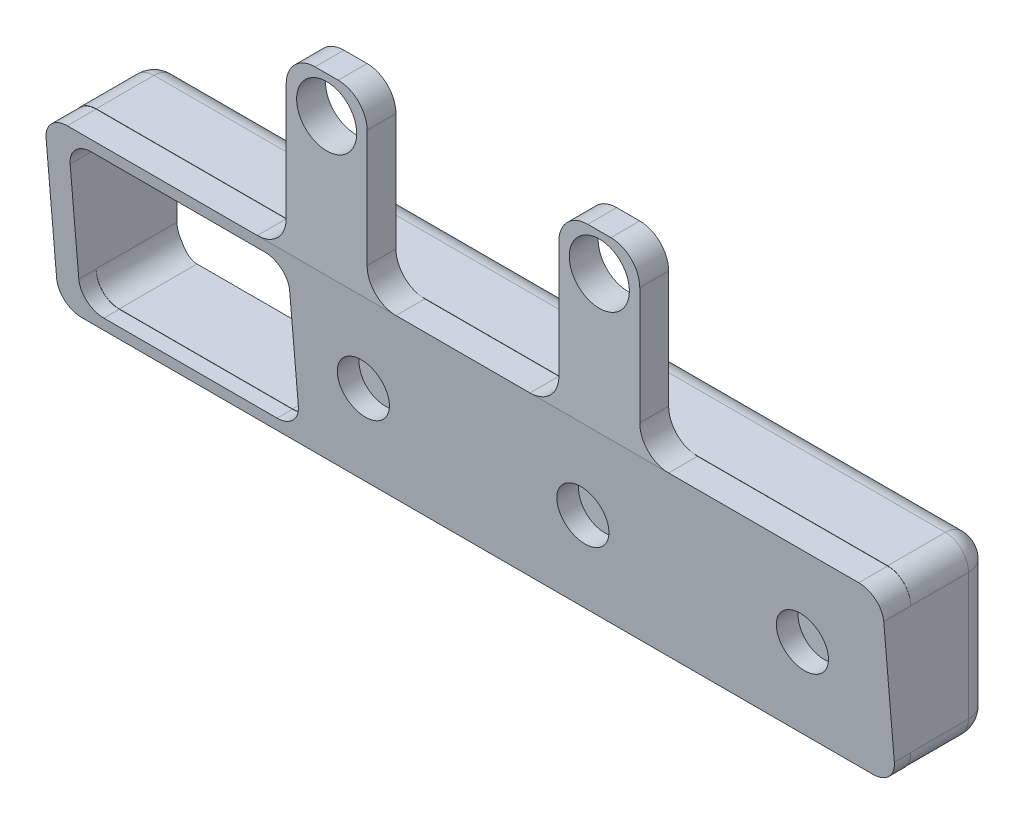
SolidWorks part; units mm, degrees
ref_plane "Front Plane" through (0, 0, 0) normal (0, 0, 1) x (1, 0, 0)
ref_plane "Top Plane" through (0, 0, 0) normal (0, 1, 0) x (1, 0, 0)
ref_plane "Right Plane" through (0, 0, 0) normal (1, 0, 0) x (0, 0, -1)
sketch "Sketch1" plane through (0, 0, 0) normal (0, 0, 1) x (1, 0, 0)
  line L0 (10.0074, 11.5687) -> (10.0074, -3.4313) construction
  line L1 (-24.2426, 11.5687) -> (-7.7926, 11.5687)
  line L2 (-26.2426, 9.5687) -> (-26.2426, -1.4313)
  line L3 (-24.2426, -3.4313) -> (44.2574, -3.4313)
  line L4 (46.2574, 9.5687) -> (46.2574, -1.4313)
  line L5 (-5.2926, 14.0687) -> (-5.2926, 24.2087)
  line L6 (-22.2426, 10.5687) -> (-7.2426, 10.5687)
  line L7 (-24.2426, 8.5687) -> (-24.2426, -0.4313)
  line L8 (-22.2426, -2.4313) -> (-7.2426, -2.4313)
  line L9 (-5.2426, 8.5687) -> (-5.2426, -0.4313)
  line L10 (-2.7926, 26.7087) -> (-0.7926, 26.7087)
  line L11 (1.7074, 24.2087) -> (1.7074, 14.0687)
  line L12 (18.3074, 14.0687) -> (18.3074, 24.2087)
  line L13 (20.8074, 26.7087) -> (22.8074, 26.7087)
  line L14 (25.3074, 24.2087) -> (25.3074, 14.0687)
  line L15 (4.2074, 11.5687) -> (15.8074, 11.5687)
  line L16 (27.8074, 11.5687) -> (44.2574, 11.5687)
  circle A0 centre (38.7574, 4.0687) radius 2.25
  circle A1 centre (19.7574, 4.0687) radius 2.25
  circle A2 centre (0.7574, 4.0687) radius 2.25
  arc A3 (-24.2426, -0.4313) -> (-22.2426, -2.4313) centre (-22.2426, -0.4313) ccw
  arc A4 (-7.2426, -2.4313) -> (-5.2426, -0.4313) centre (-7.2426, -0.4313) ccw
  arc A5 (-7.2426, 10.5687) -> (-5.2426, 8.5687) centre (-7.2426, 8.5687) cw
  arc A6 (-22.2426, 10.5687) -> (-24.2426, 8.5687) centre (-22.2426, 8.5687) ccw
  arc A7 (44.2574, -3.4313) -> (46.2574, -1.4313) centre (44.2574, -1.4313) ccw
  arc A8 (44.2574, 11.5687) -> (46.2574, 9.5687) centre (44.2574, 9.5687) cw
  arc A9 (-26.2426, -1.4313) -> (-24.2426, -3.4313) centre (-24.2426, -1.4313) ccw
  arc A10 (-24.2426, 11.5687) -> (-26.2426, 9.5687) centre (-24.2426, 9.5687) ccw
  circle A11 centre (-1.7926, 23.5087) radius 2.6
  arc A12 (-0.7926, 26.7087) -> (1.7074, 24.2087) centre (-0.7926, 24.2087) cw
  arc A13 (-5.2926, 24.2087) -> (-2.7926, 26.7087) centre (-2.7926, 24.2087) cw
  circle A14 centre (21.8074, 23.5087) radius 2.6
  arc A15 (22.8074, 26.7087) -> (25.3074, 24.2087) centre (22.8074, 24.2087) cw
  arc A16 (18.3074, 24.2087) -> (20.8074, 26.7087) centre (20.8074, 24.2087) cw
  arc A17 (25.3074, 14.0687) -> (27.8074, 11.5687) centre (27.8074, 14.0687) ccw
  arc A18 (18.3074, 14.0687) -> (15.8074, 11.5687) centre (15.8074, 14.0687) cw
  arc A19 (1.7074, 14.0687) -> (4.2074, 11.5687) centre (4.2074, 14.0687) ccw
  arc A20 (-5.2926, 14.0687) -> (-7.7926, 11.5687) centre (-7.7926, 14.0687) cw
  point P16 (-26.2426, 4.0687)
  point P29 (46.2574, 11.5687)
  point P32 (-26.2426, -3.4313)
  point P35 (-26.2426, 11.5687)
  point P44 (1.7074, 26.7087)
  point P47 (-5.2926, 26.7087)
  point P62 (25.3074, 11.5687)
  point P65 (18.3074, 11.5687)
  point P68 (1.7074, 11.5687)
  dimension "D3" = 4.5
  dimension "D6" = 4.5
  dimension "D8" = 19
  dimension "D9" = 4.5
  dimension "D15" = 2
  dimension "D16" = 2
  dimension "D17" = 5.2
  dimension "D21" = 2.5
  dimension "D23" = 5.2
  dimension "D28" = 2.5
  dimension "D1" = 72.5
  dimension "D2" = 15
  dimension "D4" = 7.5
  dimension "D5" = 7.5
  dimension "D7" = 19
  dimension "D10" = 9.25
  dimension "D11" = 1
  dimension "D12" = 1
  dimension "D13" = 2
  dimension "D14" = 21
  dimension "D18" = 7
  dimension "D19" = 3.2
  dimension "D20" = 3.5
  dimension "D22" = 3.2
  dimension "D24" = 3.5
  dimension "D25" = 7
  dimension "D26" = 23.6
  dimension "D27" = 11.8
extrude "Boss-Extrude1" add sketch "Sketch1" along normal blind 2.5
sketch "Sketch2" plane through (0, 0, 0) normal (0, 0, -1) x (-1, 0, 0)
  line L1 (-44.2574, 11.592) -> (24.2426, 11.592)
  line L2 (-46.2574, 9.592) -> (-46.2574, -1.408)
  line L3 (-44.2574, -3.408) -> (24.2426, -3.408)
  line L4 (26.2426, 9.592) -> (26.2426, -1.408)
  line L5 (7.2426, 10.592) -> (22.2426, 10.592)
  line L6 (5.2426, 8.592) -> (5.2426, -0.408)
  line L7 (7.2426, -2.408) -> (22.2426, -2.408)
  line L8 (24.2426, 8.592) -> (24.2426, -0.408)
  arc A0 (24.2426, 11.592) -> (26.2426, 9.592) centre (24.2426, 9.592) cw
  arc A1 (24.2426, -3.408) -> (26.2426, -1.408) centre (24.2426, -1.408) ccw
  arc A2 (-46.2574, -1.408) -> (-44.2574, -3.408) centre (-44.2574, -1.408) ccw
  arc A3 (-44.2574, 11.592) -> (-46.2574, 9.592) centre (-44.2574, 9.592) ccw
  arc A4 (5.2426, -0.408) -> (7.2426, -2.408) centre (7.2426, -0.408) ccw
  arc A5 (22.2426, -2.408) -> (24.2426, -0.408) centre (22.2426, -0.408) ccw
  arc A6 (22.2426, 10.592) -> (24.2426, 8.592) centre (22.2426, 8.592) cw
  arc A7 (7.2426, 10.592) -> (5.2426, 8.592) centre (7.2426, 8.592) ccw
  point P20 (24.2426, -2.408)
  point P23 (24.2426, 10.592)
  dimension "D2" = 2
  dimension "D7" = 2
  dimension "D1" = 72.5
  dimension "D3" = 15
  dimension "D4" = 19
  dimension "D5" = 13
  dimension "D6" = 2
  dimension "D8" = 1
extrude "Boss-Extrude2" add sketch "Sketch2" along normal blind 7
sketch "Sketch3" plane through (-26.2426, 0, 0) normal (-1, 0, 0) x (0, 0, 1)
  line L0 (2.5, 11.5687) -> (1.25, -3.4313)
  line L1 (2.5, -3.4313) -> (0, -3.4313) construction
  line L2 (1.25, -3.4313) -> (2.5, -3.4313)
  line L3 (2.5, -3.4313) -> (2.5, 11.5687)
extrude "Cut-Extrude1" cut sketch "Sketch3" against normal through all
fillet "Fillet1" radius 2 8 edges at (-25.6568, 11.0062, -7) (-26.2426, 4.092, -7) (-25.6568, -2.8222, -7) (10.0074, -3.408, -7) (45.6716, -2.8222, -7) (46.2574, 4.092, -7) (45.6716, 11.0062, -7) (10.0074, 11.592, -7)
